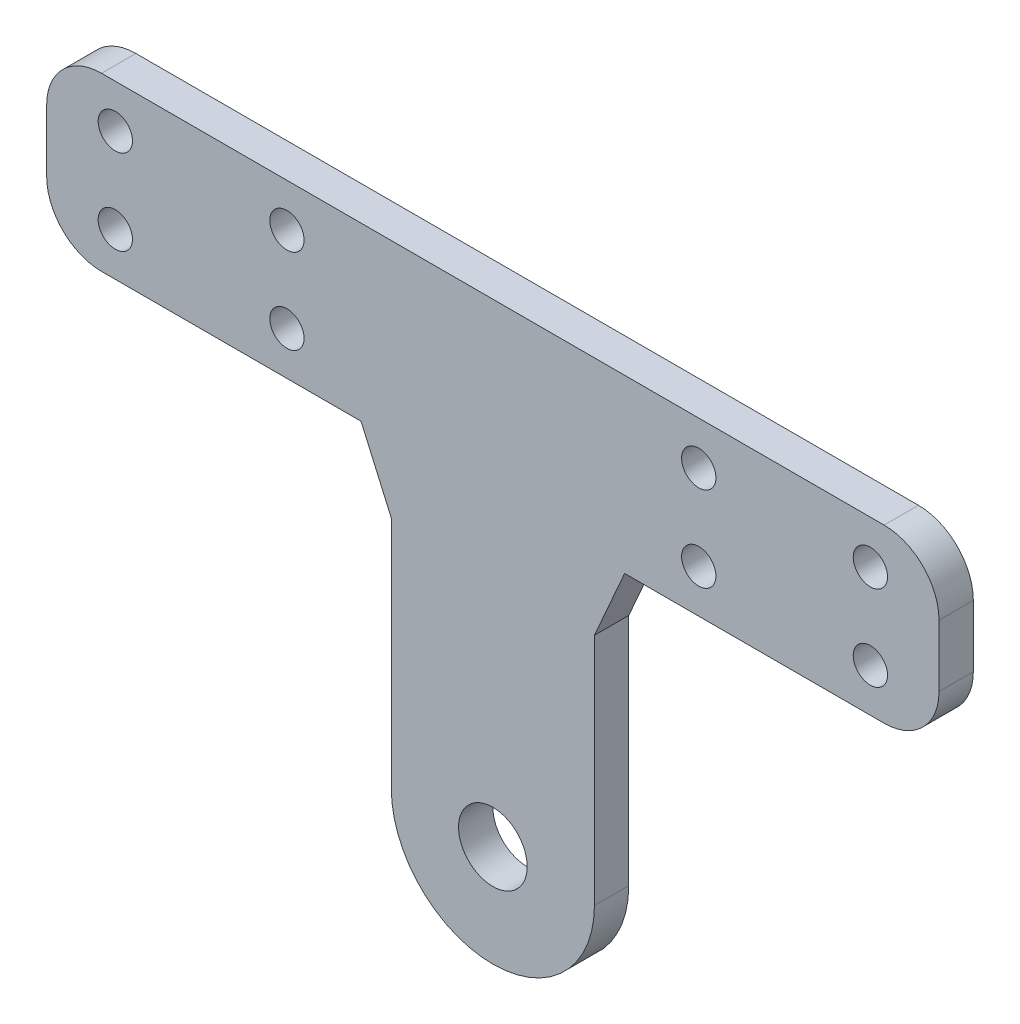
SolidWorks part; units mm, degrees
ref_plane "Front" through (0, 0, 0) normal (0, 0, 1) x (1, 0, 0)
ref_plane "Top" through (0, 0, 0) normal (0, 1, 0) x (1, 0, 0)
ref_plane "Right" through (0, 0, 0) normal (1, 0, 0) x (0, 0, -1)
ref_axis "side-side" through (80.9, 0, 0) along (-1, 0, 0)
ref_axis "up-down" through (0, 50, 0) along (0, -1, 0)
ref_axis "front-back" through (0, 0, -80.9) along (0, 0, 1)
sketch "Sketch1" plane through (0, 0, 0) normal (0, 0, 1) x (1, 0, 0)
  line L0 (0, 0) -> (0, 43.879) construction
  line L1 (-41.275, 43.879) -> (41.275, 43.879)
  line L2 (-41.275, 43.879) -> (-41.275, 28.004)
  line L3 (-41.275, 28.004) -> (-12.192, 28.004)
  line L4 (41.275, 43.879) -> (41.275, 28.004)
  line L5 (-41.275, 16.6097) -> (-28.575, 16.6097) construction
  line L6 (-41.275, 16.6097) -> (-41.275, 2.1106) construction
  line L7 (-41.275, 2.1106) -> (-28.575, 2.1106) construction
  line L8 (-28.575, 16.6097) -> (-28.575, 2.1106) construction
  line L9 (-25.4, 16.6097) -> (-12.7, 16.6097) construction
  line L10 (-25.4, 16.6097) -> (-25.4, 0) construction
  line L11 (-25.4, 0) -> (-12.7, 0) construction
  line L12 (-12.7, 16.6097) -> (-12.7, 0) construction
  line L13 (-12.192, 28.004) -> (-9.398, 21.654)
  line L14 (-9.398, 21.654) -> (-9.398, 0)
  line L15 (9.398, 0) -> (9.398, 21.654)
  line L16 (9.398, 21.654) -> (12.192, 28.004)
  line L17 (12.192, 28.004) -> (41.275, 28.004)
  circle A0 centre (0, 0) radius 3.175
  circle A1 centre (-19.05, 32.004) radius 1.5875
  circle A2 centre (-34.925, 32.004) radius 1.5875
  arc A3 (-9.398, 0) -> (9.398, 0) centre (0, 0) ccw
  circle A4 centre (34.925, 32.004) radius 1.5875
  circle A5 centre (19.05, 32.004) radius 1.5875
  circle A6 centre (-19.05, 39.879) radius 1.5875
  circle A7 centre (-34.925, 39.879) radius 1.5875
  circle A8 centre (34.925, 39.879) radius 1.5875
  circle A9 centre (19.05, 39.879) radius 1.5875
  point P17 (-19.05, 16.6097)
  point P18 (-34.925, 16.6097)
  point P41 (0, 0)
  point P42 (0, 0)
  point P43 (0, 0)
  dimension "D1" = 6.35
  dimension "D2" = 3.175
  dimension "D5" = 4
  dimension "D7" = 32.004
  dimension "D14" = 53.975
  dimension "D3" = 12.7
  dimension "D4" = 15.875
  dimension "D6" = 12.7
  dimension "D8" = 15.875
  dimension "D9" = 18.796
  dimension "D10" = 6.35
  dimension "D11" = 12.192
  dimension "D12" = 4
  dimension "D13" = 19.05
extrude "Boss-Extrude1" add sketch "Sketch1" along normal blind 3.175
fillet "Fillet1" radius 5.08 4 edges at (41.275, 28.004, 1.5875) (41.275, 43.879, 1.5875) (-41.275, 28.004, 1.5875) (-41.275, 43.879, 1.5875)
